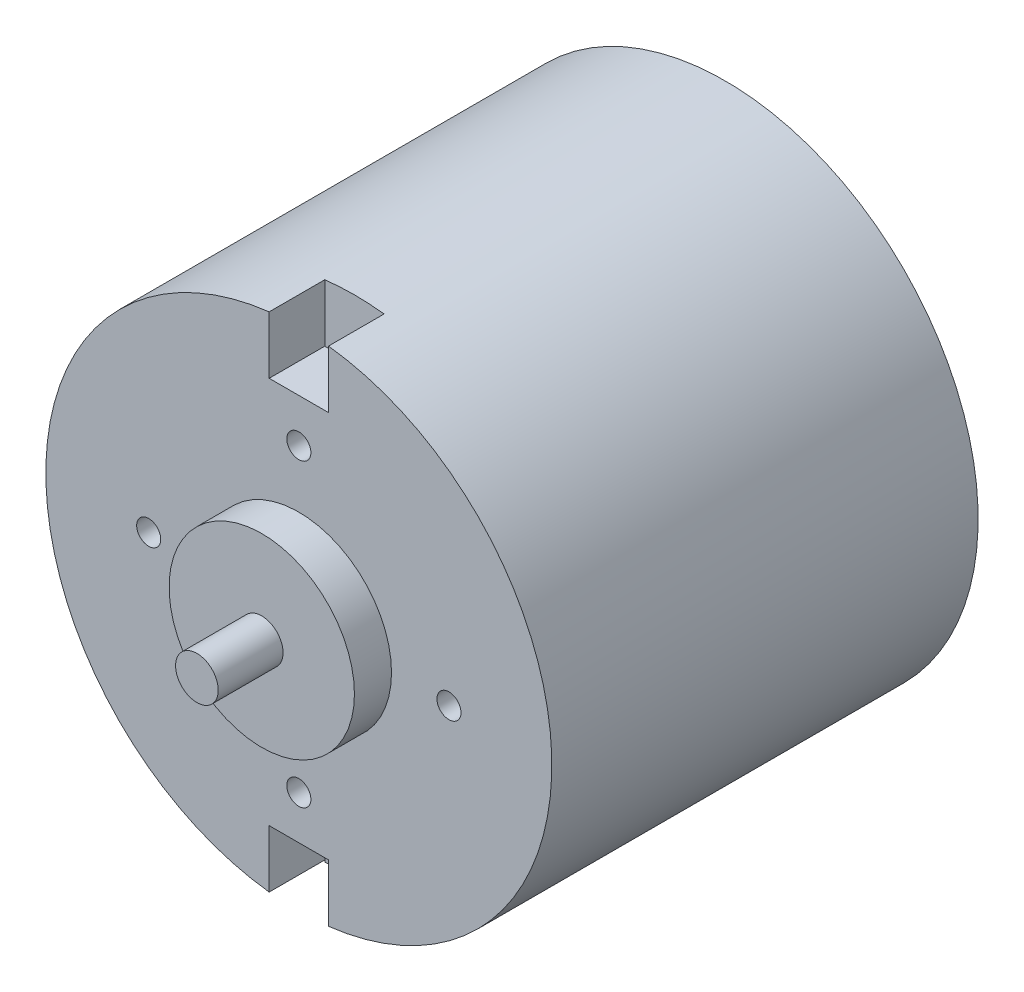
SolidWorks part; units mm, degrees
ref_plane "Front Plane" through (0, 0, 0) normal (0, 0, 1) x (1, 0, 0)
ref_plane "Top Plane" through (0, 0, 0) normal (0, 1, 0) x (1, 0, 0)
ref_plane "Right Plane" through (0, 0, 0) normal (1, 0, 0) x (0, 0, -1)
sketch "Sketch1" plane through (0, 0, 0) normal (0, 0, 1) x (1, 0, 0)
  line L1 (-1.6, 13.65) -> (1.6, 13.65)
  line L2 (-1.6, 13.65) -> (-1.6, 10.45)
  line L3 (-1.6, 10.45) -> (1.6, 10.45)
  line L4 (1.6, 13.65) -> (1.6, 10.45)
  line L5 (-1.6, -13.65) -> (1.6, -13.65)
  line L6 (-1.6, -13.65) -> (-1.6, -10.45)
  line L7 (-1.6, -10.45) -> (1.6, -10.45)
  line L8 (1.6, -13.65) -> (1.6, -10.45)
  circle A0 centre (0, 0) radius 13.65
  circle A1 centre (0, 0) radius 5
  circle A2 centre (0, 0) radius 1.15
  circle A3 centre (0, 8.1) radius 0.65
  circle A4 centre (0, -8.1) radius 0.65
  circle A5 centre (-8.1, 0) radius 0.65
  circle A6 centre (8.1, 0) radius 0.65
  point P17 (0, 13.65)
  point P22 (0, -13.65)
  dimension "D1" = 27.3
  dimension "D2" = 10
  dimension "D3" = 2.3
  dimension "D4" = 8.1
  dimension "D8" = 1.3
  dimension "D5" = 8.1
  dimension "D6" = 8.1
  dimension "D7" = 8.1
  dimension "D9" = 3.2
  dimension "D10" = 3.2
extrude "Boss-Extrude1" add sketch "Sketch1" along normal blind 3 contours L2 A0 L6 L7 L8 L4 L3 A6 A5 A4 A3 A1 | A1 A2 | A2 region at (-1.9848, 12.003, 0) region at (-4.8586, 0, 0) region at (0, 0, 0)
extrude "Boss-Extrude2" add sketch "Sketch1<3>" against normal blind 20 contours L4 A0 L2 L3 | L2 A0 L6 L7 L8 L4 L3 A6 A5 A4 A3 A1 | A1 A2 | A2 | A4 | A5 | L6 L7 L8 L5 | A6 | A3 region at (0, 12.0345, 0) region at (-1.9848, 12.003, 0) region at (-4.8586, 0, 0) region at (0, 0, 0) region at (0, -8.1, 0) region at (-8.1, 0, 0)
sketch "Sketch1<3>" plane through (0, 0, 0) normal (0, 0, 1) x (1, 0, 0) same geometry as "Sketch1"
extrude "Boss-Extrude3" add sketch "Sketch1<4>" along normal blind 5 contours A1 A2 region at (-4.8586, 0, 0)
sketch "Sketch1<4>" plane through (0, 0, 0) normal (0, 0, 1) x (1, 0, 0) same geometry as "Sketch1"
extrude "Boss-Extrude4" add sketch "Sketch1<5>" along normal blind 8.5 contours A2
sketch "Sketch1<5>" plane through (0, 0, 0) normal (0, 0, 1) x (1, 0, 0) same geometry as "Sketch1"
